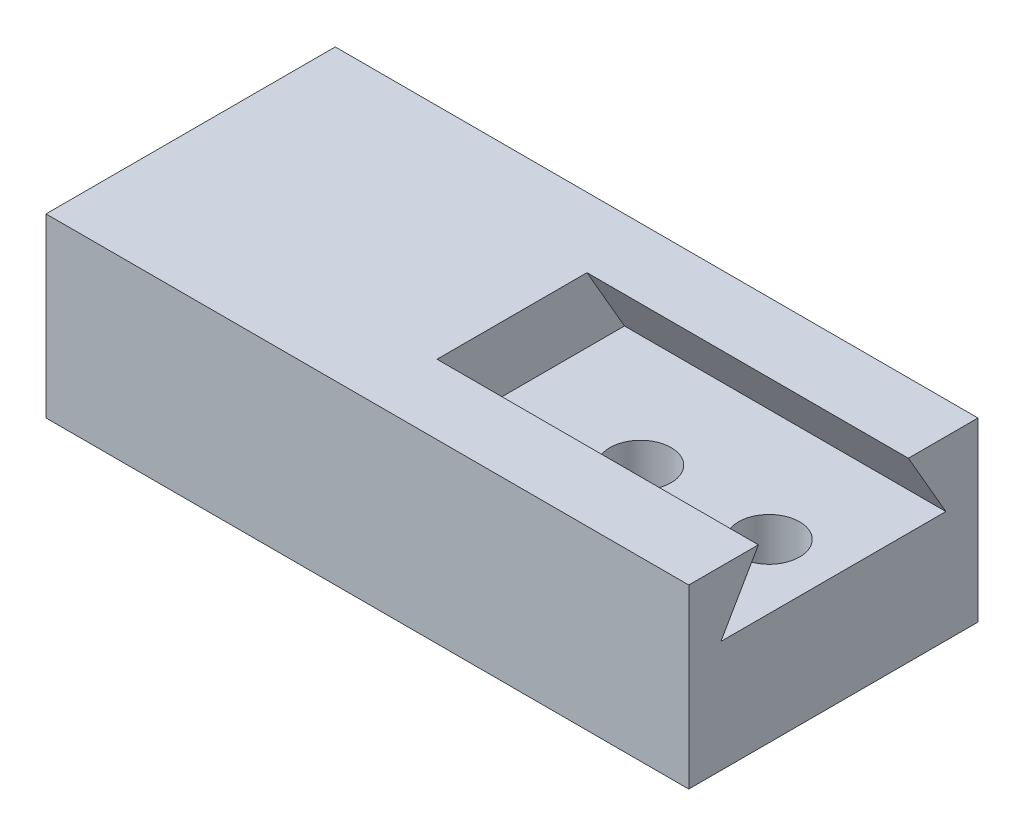
SolidWorks part; units mm, degrees
ref_plane "Front Plane" through (0, 0, 0) normal (0, 0, 1) x (1, 0, 0)
ref_plane "Top Plane" through (0, 0, 0) normal (0, 1, 0) x (1, 0, 0)
ref_plane "Right Plane" through (0, 0, 0) normal (1, 0, 0) x (0, 0, -1)
sketch "base_sketch" plane through (0, 0, 0) normal (1, 0, 0) x (0, 0, -1)
  line L1 (0, 2.0207) -> (-1.75, -1.0104)
  line L2 (-1.75, -1.0104) -> (1.75, -1.0104)
  line L3 (1.75, -1.0104) -> (0, 2.0207)
  line L8 (-2.25, 0) -> (2.25, 0)
  line L9 (-2.25, 0) -> (-2.25, -2.75)
  line L10 (-2.25, -2.75) -> (2.25, -2.75)
  line L11 (2.25, 0) -> (2.25, -2.75)
  line L12 (-2.25, 0) -> (2.25, -2.75) construction
  line L13 (-2.25, -2.75) -> (2.25, 0) construction
  circle A0 centre (0, 0) radius 1.0104 construction
  point P1 (0, -1.375)
  dimension "D2" = 3.5
  dimension "D1" = 4.5
  dimension "D3" = 0
  dimension "D4" = 2.75
extrude "ledge_extrude" [suppressed] add sketch "base_sketch" along normal blind 5 contours L8 L1 L2 L3
sketch "sketch_thinning" [suppressed] plane through (5, 0, 0) normal (1, 0, 0) x (0, 0, -1)
  line L8 (1.1089, -0.1) -> (-1.1089, -0.1)
  line L9 (-1.1089, -0.1) -> (-1.5768, -0.9104)
  line L10 (-1.5768, -0.9104) -> (1.5768, -0.9104)
  line L11 (1.5768, -0.9104) -> (1.1089, -0.1)
  line L12 (1.1089, -0.1) -> (-1.1089, -0.1)
  line L13 (-1.1089, -0.1) -> (-1.5768, -0.9104)
  line L14 (-1.5768, -0.9104) -> (1.5768, -0.9104)
  line L15 (1.5768, -0.9104) -> (1.1089, -0.1)
  dimension "D1" = 0.1
extrude "thinning" [suppressed] cut sketch "sketch_thinning" against normal up to next flip side to cut
extrude "Boss-Extrude1" add sketch "base_sketch<3>" along normal blind 5 contours L11 L8 L3 L2 L1 L9 L10 region at (0, -1.6363, 0)
sketch "base_sketch<3>" plane through (0, 0, 0) normal (1, 0, 0) x (0, 0, -1) same geometry as "base_sketch"
extrude "Boss-Extrude2" add sketch "base_sketch<4>" against normal blind 5 contours L9 L10 L11 L8
sketch "base_sketch<4>" plane through (0, 0, 0) normal (1, 0, 0) x (0, 0, -1) same geometry as "base_sketch"
hole_wizard "Tap Drill for M1.2x0.25 Tap1" positions "Sketch2" profile "Sketch3" hole size "M1.2x0.25" standard "ANSI Metric" end condition up to next
sketch "Sketch2" plane through (0, -2.75, 0) normal (0, -1, 0) x (-1, 0, 0)
  line L0 (-5, -2.25) -> (-5, 2.25) construction
  point P0 (-4, 0)
  point P2 (-2, 0)
  point P6 (-5, 0)
  dimension "D1" = 1
  dimension "D2" = 2
sketch "Sketch3" plane through (4, -2.75, 0) normal (1, 0, 0) x (0, 0, -1)
  line L0 (0, 0) -> (0, 1.7396)
  line L1 (0, 1.7396) -> (0.475, 1.7396)
  line L2 (0.475, 1.7396) -> (0.475, 0)
  line L5 (0.475, 0) -> (0, 0)
  line L11 (0, -6.35) -> (0, 107.95) construction
  dimension "Thru Hole Dia." = 0.95
  dimension "Thru Hole Depth" = 1.7396
equation "\"D1@base_sketch\" = \"D2@base_sketch\" + 1"
